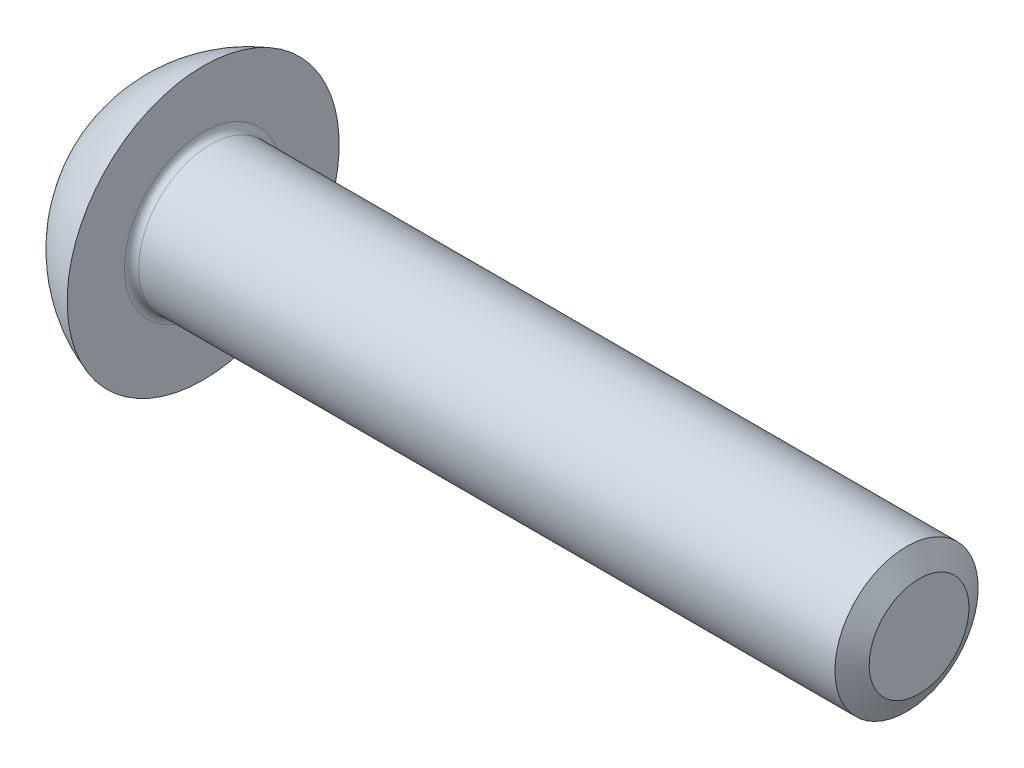
SolidWorks part; units mm, degrees
ref_plane "前视基准面" through (0, 0, 0) normal (0, 0, 1) x (1, 0, 0)
ref_plane "上视基准面" through (0, 0, 0) normal (0, 1, 0) x (1, 0, 0)
ref_plane "右视基准面" through (0, 0, 0) normal (1, 0, 0) x (0, 0, -1)
sketch "尺寸草图" plane through (0, 0, 0) normal (0, 0, 1) x (1, 0, 0)
  line L0 (0, 0) -> (20, 0) construction
  line L1 (20, 0) -> (20, 2) construction
  line L2 (20, 2) -> (19.3, 2) construction
  line L3 (0, 0) -> (0, 3.8) construction
  point P3 (1.4, 0)
  point P6 (20, 2.35)
  point P7 (0, 0.93)
  point P9 (2.2, 0)
  point P10 (2.4, 0)
  point P11 (20, 1.25)
  point P12 (3.7, 0)
  point P13 (4, 0)
  point P14 (20, 22.35)
  dimension "l" = 20
  dimension "d" = 4
  dimension "P" = 0.7
  dimension "a" = 1.4
  dimension "da" = 4.7
  dimension "dk" = 7.6
  dimension "e" = 2.87
  dimension "K" = 2.2
  dimension "r" = 0.2
  dimension "s" = 2.5
  dimension "t" = 1.3
  dimension "w" = 0.3
  dimension "zslwx" = 20
sketch "草图1" plane through (0, 0, 0) normal (0, 0, 1) x (1, 0, 0)
  line L0 (-22.2, 0) -> (0, 0) construction
  line L1 (0, 2) -> (-19.8, 2)
  line L2 (-20, 2.2) -> (-20, 3.8)
  line L3 (-22.2, 0) -> (-22.2, 2)
  line L4 (0, 2) -> (0, 0)
  line L5 (-22.2, 0) -> (0, 0)
  arc A0 (-20, 3.8) -> (-22.2, 2) centre (-18.7273, 0) ccw
  arc A1 (-19.8, 2) -> (-20, 2.2) centre (-19.8, 2.2) cw
  point P10 (-20, 2)
  dimension "r" = 0.2
  dimension "d" = 4
  dimension "dk" = 7.6
  dimension "k" = 2.2
  dimension "l" = 20
revolve "旋转1" add sketch "草图1" angle 360 about L0
cosmetic thread "装饰螺纹线1" parameters "D1"=20, "D2"=3.44
sketch "草图2" plane through (-22.2, 0, 0) normal (-1, 0, 0) x (0, 0, 1)
  line L1 (0, 1.4434) -> (-1.25, 0.7217)
  line L2 (-1.25, 0.7217) -> (-1.25, -0.7217)
  line L3 (-1.25, -0.7217) -> (0, -1.4434)
  line L4 (0, -1.4434) -> (1.25, -0.7217)
  line L5 (1.25, -0.7217) -> (1.25, 0.7217)
  line L6 (1.25, 0.7217) -> (0, 1.4434)
  circle A0 centre (0, 0) radius 1.25 construction
  dimension "s" = 2.5
extrude "切除-拉伸1" cut sketch "草图2" against normal blind 2.2
sketch "草图6" plane through (0, 0, 0) normal (0, 0, 1) x (1, 0, 0)
  line L0 (-20.9, 1.4434) -> (-20, 0)
  line L1 (-19.63, 1.4434) -> (-19.63, 0)
  line L2 (-19.63, 1.4434) -> (-20.9, 1.4434)
  line L3 (-22.2, 0) -> (-20, 0) construction
  line L4 (-19.63, 0) -> (-20, 0)
  line L5 (-22.2, 0) -> (-25.07, 0) construction
  dimension "t" = 1.3
  dimension "e-s" = 0.37
  dimension "k" = 2.2
  dimension "e" = 2.87
revolve "旋转2" add sketch "草图6" angle 360 about L3
sketch "草图7" plane through (0, 0, 0) normal (0, 0, 1) x (1, 0, 0)
  line L3 (-22.2, 1.4434) -> (-21.83, 0)
  line L4 (-22.2, 0) -> (-21.83, 0) construction
  line L7 (-22.2, 1.4434) -> (-22.2, 0)
  line L8 (-22.2, 0) -> (-21.83, 0)
  dimension "e-s" = 0.37
revolve "切除-旋转5" cut sketch "草图7" angle 360 about L4
sketch "草图4" plane through (0, 0, 0) normal (0, 0, 1) x (1, 0, 0)
  line L0 (-0.35, 2) -> (0, 1.3938)
  line L1 (-0.35, 2) -> (0.35, 2)
  line L2 (0.35, 2) -> (0, 1.3938)
  line L4 (0, -2) -> (0, 2) construction
  line L5 (-0.35, 0) -> (0.35, 0) construction
  dimension "d" = 2
  dimension "p" = 0.7
revolve "切除-旋转1" cut sketch "草图4" angle 360 about L5
ref_axis "基准轴1" through (-8.1887, 0, 0) along (1, 0, 0)
pattern_linear "阵列(线性)1" [suppressed] count 27 spacing 0.7 along (-1, 0, 0) of bodies 104
